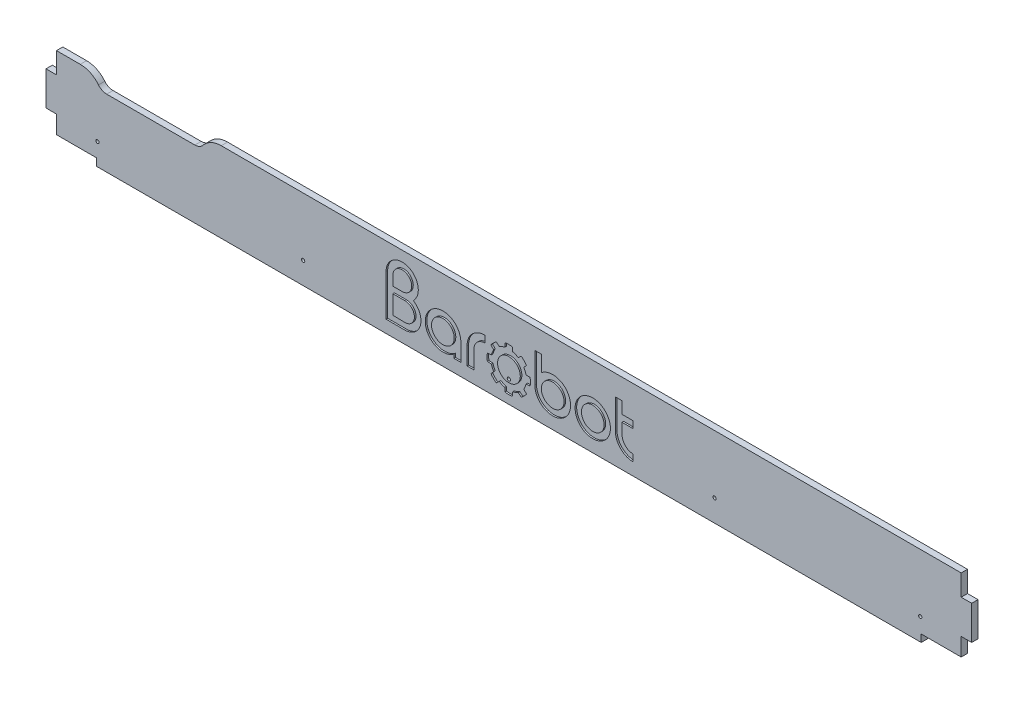
SolidWorks part; units mm, degrees
ref_plane "Płaszczyzna przednia" through (0, 0, 0) normal (0, 0, 1) x (1, 0, 0)
ref_plane "Płaszczyzna górna" through (0, 0, 0) normal (0, 1, 0) x (1, 0, 0)
ref_plane "Płaszczyzna prawa" through (0, 0, 0) normal (1, 0, 0) x (0, 0, -1)
sketch "Szkic2" plane through (0, 0, 0) normal (0, 0, 1) x (1, 0, 0)
  line L36 (-832, -462.604) -> (-48, -462.604)
  line L37 (-48, -462.604) -> (-48, -455.604)
  line L38 (-48, -455.604) -> (-10, -455.604)
  line L39 (-10, -455.604) -> (-10, -448.104)
  line L40 (-10, -438.604) -> (0, -438.604)
  line L41 (0, -438.604) -> (0, -406.324)
  line L42 (0, -406.324) -> (-10, -406.324)
  line L43 (-10, -406.324) -> (-10, -399.424)
  line L44 (-10, -386.324) -> (-713.4049, -386.324)
  line L45 (-738.497, -398.324) -> (-822.3149, -398.324)
  line L46 (-847.407, -386.324) -> (-870, -386.324)
  line L47 (-870, -386.324) -> (-870, -396.324)
  line L48 (-870, -406.324) -> (-880, -406.324)
  line L49 (-880, -406.324) -> (-880, -438.604)
  line L50 (-880, -438.604) -> (-870, -438.604)
  line L51 (-870, -438.604) -> (-870, -445.004)
  line L52 (-870, -455.604) -> (-832, -455.604)
  line L53 (-832, -455.604) -> (-832, -462.604)
  line L102 (-870, -396.324) -> (-870, -399.424)
  line L103 (-870, -445.004) -> (-870, -448.104)
  line L105 (-10, -396.324) -> (-10, -399.424)
  line L106 (-10, -445.004) -> (-10, -448.104)
  line L173 (-870, -448.104) -> (-870, -455.604)
  line L197 (-10, -445.004) -> (-10, -438.604)
  line L221 (-10, -396.324) -> (-10, -386.324)
  line L245 (-870, -399.424) -> (-870, -406.324)
  arc A8 (-713.4049, -386.324) -> (-730.7126, -394.6012) centre (-713.4049, -408.5578) ccw
  arc A9 (-738.497, -398.324) -> (-730.7126, -394.6012) centre (-738.497, -388.324) ccw
  arc A10 (-830.0993, -394.6012) -> (-822.3149, -398.324) centre (-822.3149, -388.324) ccw
  arc A11 (-830.0993, -394.6012) -> (-847.407, -386.324) centre (-847.407, -408.5578) ccw
extrude "Dodanie-wyciągnięcie1" add sketch "Szkic2" along normal blind 6
sketch "Szkic3" plane through (0, 0, 6) normal (0, 0, 1) x (1, 0, 0)
  circle A0 centre (-635.558, -441.7627) radius 1.55 construction
  circle A1 centre (-831.114, -441.7627) radius 1.55 construction
  circle A2 centre (-440.002, -441.7627) radius 1.55 construction
  circle A3 centre (-244.446, -441.7627) radius 1.55 construction
  circle A4 centre (-48.89, -441.7627) radius 1.55 construction
  circle A5 centre (-635.558, -441.7627) radius 1.55
  circle A6 centre (-831.114, -441.7627) radius 1.55
  circle A7 centre (-440.002, -441.7627) radius 1.55
  circle A8 centre (-244.446, -441.7627) radius 1.55
  circle A9 centre (-48.89, -441.7627) radius 1.55
extrude "Wytnij-wyciągnięcie1" cut sketch "Szkic3" against normal blind 6
sketch "Szkic18" plane through (0, 0, 6) normal (0, 0, 1) x (1, 0, 0)
  line L0 (-408.8752, -420.6037) -> (-408.8752, -420.833)
  line L2 (-550.3017, -411.4261) -> (-550.3017, -420.3981)
  line L3 (-550.3017, -444.3866) -> (-538.7617, -444.5821)
  line L4 (-541.3297, -420.3981) -> (-550.3017, -420.3981)
  line L5 (-538.7617, -426.6381) -> (-550.3017, -426.6381)
  line L6 (-550.3017, -426.6381) -> (-550.3017, -444.3866)
  circle A0 centre (-439.9185, -433.9811) radius 10.8
  circle A1 centre (-398.3185, -434.1758) radius 10.8
  circle A2 centre (-360.2385, -434.1673) radius 10.8
  circle A3 centre (-502.7185, -433.9811) radius 10.8
  arc A4 (-539.0655, -444.5769) -> (-538.7617, -426.6381) centre (-538.7617, -435.6101) ccw
  arc A5 (-541.3297, -420.3981) -> (-550.3017, -411.4261) centre (-541.3297, -411.4261) ccw
  circle A6 centre (-360.2385, -434.1673) radius 16.7971
  arc A7 (-321.883, -450.8241) -> (-338.774, -434.1673) centre (-321.8529, -433.9009) cw
  arc A8 (-415.3324, -434.1758) -> (-408.8752, -420.833) centre (-398.3185, -434.1758) ccw
  spline S0 degree 3 poles (-548.0079, -397.6111) (-547.8784, -397.5486) (-547.6175, -397.4274) (-547.2212, -397.257) (-546.8201, -397.0982) (-546.4147, -396.951) (-546.0053, -396.8154) (-545.5921, -396.6915) (-545.1757, -396.5793) (-544.7562, -396.4789) (-544.3341, -396.3904) (-543.9096, -396.3137) (-543.4832, -396.249) (-543.0551, -396.1962) (-542.6257, -396.1555) (-542.1953, -396.1269) (-541.7643, -396.1104) (-541.333, -396.1062) (-540.9017, -396.1141) (-540.4708, -396.1344) (-540.0406, -396.167) (-539.7546, -396.197) (-539.6118, -396.2141) knots 0 0 0 0 0.021232 0.042459 0.063684 0.084907 0.10613 0.127352 0.148575 0.169797 0.191021 0.212245 0.233469 0.254693 0.275917 0.297141 0.318365 0.33959 0.360814 0.38204 0.403268 0.424499 0.424499 0.424499 0.424499
  spline S1 degree 3 poles (-539.6118, -396.2141) (-539.4388, -396.2328) (-539.0937, -396.2767) (-538.5787, -396.3611) (-538.0672, -396.464) (-537.5598, -396.5849) (-537.0568, -396.7235) (-536.559, -396.8796) (-536.0668, -397.0529) (-535.5808, -397.243) (-535.1016, -397.4497) (-534.6296, -397.6726) (-534.1654, -397.9115) (-533.7096, -398.1661) (-533.2626, -398.436) (-532.8251, -398.721) (-532.3976, -399.0207) (-531.9806, -399.3349) (-531.5747, -399.6633) (-531.1804, -400.0055) (-530.7983, -400.3613) (-530.552, -400.6073) (-530.4311, -400.7325) knots 0 0 0 0 0.025683 0.051357 0.077025 0.102692 0.128359 0.154029 0.179702 0.205379 0.23106 0.256745 0.282432 0.308121 0.333811 0.359502 0.385192 0.410881 0.436569 0.462257 0.487946 0.513638 0.513638 0.513638 0.513638
  spline S2 degree 3 poles (-530.4311, -400.7325) (-530.302, -400.8635) (-530.0489, -401.1305) (-529.6846, -401.5448) (-529.3361, -401.9724) (-529.0037, -402.4124) (-528.6877, -402.8643) (-528.3885, -403.3273) (-528.1062, -403.8009) (-527.8411, -404.2844) (-527.5937, -404.7772) (-527.3642, -405.2784) (-527.1528, -405.7876) (-526.9599, -406.3041) (-526.7858, -406.8272) (-526.6308, -407.3562) (-526.4952, -407.8905) (-526.3792, -408.4295) (-526.2832, -408.9725) (-526.2075, -409.5187) (-526.1523, -410.0677) (-526.1295, -410.4349) (-526.1216, -410.6187) knots 0 0 0 0 0.027156 0.0543 0.081437 0.108569 0.135698 0.162826 0.189954 0.217081 0.244209 0.271336 0.298463 0.325588 0.352712 0.379836 0.406959 0.434083 0.46121 0.488344 0.515488 0.542648 0.542648 0.542648 0.542648
  spline S3 degree 3 poles (-526.1216, -410.6187) (-526.1122, -410.7808) (-526.099, -411.1051) (-526.0954, -411.5919) (-526.1078, -412.0782) (-526.136, -412.5637) (-526.18, -413.0479) (-526.2395, -413.5303) (-526.3145, -414.0104) (-526.4048, -414.4879) (-526.5102, -414.9623) (-526.6306, -415.433) (-526.7659, -415.8998) (-526.9159, -416.362) (-527.0804, -416.8192) (-527.2594, -417.2711) (-527.4527, -417.7171) (-527.6601, -418.1568) (-527.8815, -418.5897) (-528.1168, -419.0154) (-528.3658, -419.4334) (-528.5408, -419.7066) (-528.6305, -419.8417) knots 0 0 0 0 0.023966 0.047916 0.071852 0.09578 0.1197 0.143615 0.167527 0.191438 0.215347 0.239256 0.263166 0.287077 0.310989 0.334903 0.35882 0.38274 0.406665 0.430596 0.454535 0.478484 0.478484 0.478484 0.478484
  spline S4 degree 3 poles (-528.6305, -419.8417) (-528.6617, -419.8901) (-528.7249, -419.9862) (-528.8221, -420.1285) (-528.9217, -420.269) (-529.0232, -420.4079) (-529.1267, -420.5453) (-529.232, -420.6813) (-529.3388, -420.8161) (-529.4469, -420.9497) (-529.5564, -421.0824) (-529.6668, -421.2142) (-529.7782, -421.3452) (-529.8903, -421.4757) (-530.0029, -421.6058) (-530.1159, -421.7355) (-530.2291, -421.865) (-530.3424, -421.9944) (-530.4555, -422.124) (-530.5683, -422.2537) (-530.6807, -422.3837) (-530.7552, -422.4708) (-530.7923, -422.5144) knots 0 0 0 0 0.008494 0.016976 0.025449 0.033917 0.042381 0.050843 0.059304 0.067766 0.076228 0.084691 0.093156 0.101621 0.110087 0.118553 0.127019 0.135484 0.143948 0.152409 0.160867 0.169322 0.169322 0.169322 0.169322
  spline S5 degree 3 poles (-530.7923, -422.5144) (-530.6421, -422.6076) (-530.3449, -422.7995) (-529.9095, -423.1027) (-529.4849, -423.4209) (-529.0717, -423.7537) (-528.6702, -424.1005) (-528.2807, -424.4608) (-527.9039, -424.8343) (-527.5399, -425.2204) (-527.1894, -425.6186) (-526.8526, -426.0286) (-526.53, -426.4499) (-526.2221, -426.8818) (-525.9292, -427.3242) (-525.6517, -427.7763) (-525.3901, -428.2378) (-525.1448, -428.7083) (-524.9162, -429.1871) (-524.7047, -429.674) (-524.5108, -430.1683) (-524.3935, -430.5025) (-524.3379, -430.6706) knots 0 0 0 0 0.02611 0.052215 0.07832 0.104424 0.130528 0.156634 0.182739 0.208846 0.234952 0.261058 0.287162 0.313266 0.339368 0.365469 0.391571 0.417674 0.443782 0.469897 0.496023 0.522166 0.522166 0.522166 0.522166
  spline S6 degree 3 poles (-524.3379, -430.6706) (-524.2887, -430.8173) (-524.1948, -431.1122) (-524.0678, -431.5587) (-523.9545, -432.0088) (-523.8552, -432.462) (-523.7697, -432.9179) (-523.698, -433.3762) (-523.6402, -433.8363) (-523.5963, -434.298) (-523.5664, -434.7608) (-523.5503, -435.2242) (-523.5482, -435.6879) (-523.56, -436.1514) (-523.5857, -436.6143) (-523.6254, -437.0763) (-523.6791, -437.5368) (-523.7468, -437.9956) (-523.8285, -438.4521) (-523.9243, -438.9059) (-524.034, -439.3567) (-524.1165, -439.6549) (-524.1601, -439.8033) knots 0 0 0 0 0.022848 0.045688 0.068522 0.091351 0.114176 0.136999 0.15982 0.182639 0.205457 0.228273 0.251089 0.273904 0.296718 0.319532 0.342347 0.365163 0.387982 0.410804 0.433633 0.456469 0.456469 0.456469 0.456469
  spline S7 degree 3 poles (-524.1601, -439.8033) (-524.2091, -439.9748) (-524.3133, -440.3159) (-524.4884, -440.8213) (-524.6818, -441.3197) (-524.893, -441.8107) (-525.1216, -442.2937) (-525.3672, -442.7683) (-525.6293, -443.234) (-525.9075, -443.6903) (-526.2014, -444.1366) (-526.5107, -444.5726) (-526.8347, -444.9977) (-527.1733, -445.4114) (-527.5258, -445.8132) (-527.8919, -446.2027) (-528.2712, -446.5794) (-528.6632, -446.9427) (-529.0676, -447.2922) (-529.4838, -447.6274) (-529.9115, -447.9478) (-530.204, -448.1512) (-530.3521, -448.2502) knots 0 0 0 0 0.026332 0.052646 0.078949 0.105245 0.131537 0.157828 0.18412 0.210414 0.23671 0.263009 0.28931 0.315612 0.341914 0.368216 0.394517 0.420816 0.447113 0.473408 0.499701 0.525996 0.525996 0.525996 0.525996
  spline S8 degree 3 poles (-530.3521, -448.2502) (-530.4776, -448.3343) (-530.7314, -448.4987) (-531.1192, -448.7336) (-531.5139, -448.9567) (-531.9151, -449.1679) (-532.3223, -449.3671) (-532.7354, -449.5541) (-533.1538, -449.7288) (-533.5771, -449.8911) (-534.0051, -450.0408) (-534.4373, -450.1778) (-534.8733, -450.302) (-535.3129, -450.4132) (-535.7555, -450.5114) (-536.2009, -450.5963) (-536.6486, -450.6678) (-537.0982, -450.7259) (-537.5495, -450.7704) (-538.002, -450.8011) (-538.4553, -450.818) (-538.7578, -450.8198) (-538.909, -450.8184) knots 0 0 0 0 0.022313 0.044623 0.066933 0.089241 0.11155 0.13386 0.156169 0.178479 0.200789 0.223098 0.245408 0.267717 0.290025 0.312334 0.334643 0.356952 0.379264 0.40158 0.4239 0.446229 0.446229 0.446229 0.446229
  spline S9 degree 3 poles (-538.909, -450.8184) (-539.2052, -450.8179) (-539.7976, -450.8169) (-540.6862, -450.8161) (-541.5748, -450.8156) (-542.4633, -450.8156) (-543.3519, -450.8158) (-544.2405, -450.8163) (-545.1291, -450.8169) (-546.0177, -450.8175) (-546.9062, -450.8182) (-547.7948, -450.8188) (-548.6834, -450.8193) (-549.572, -450.8195) (-550.4605, -450.8194) (-551.3491, -450.819) (-552.2377, -450.8181) (-553.1263, -450.8167) (-554.0148, -450.8147) (-554.9034, -450.8121) (-555.792, -450.8087) (-556.3844, -450.8059) (-556.6806, -450.8043) knots 0 0 0 0 0.043729 0.087458 0.131188 0.174917 0.218646 0.262375 0.306104 0.349833 0.393563 0.437292 0.481021 0.52475 0.568479 0.612209 0.655938 0.699667 0.743396 0.787126 0.830855 0.874585 0.874585 0.874585 0.874585
  spline S10 degree 3 poles (-556.6806, -450.8043) (-556.68, -450.1497) (-556.679, -448.8405) (-556.6778, -446.8766) (-556.6768, -444.9128) (-556.6762, -442.949) (-556.6757, -440.9851) (-556.6754, -439.0213) (-556.6753, -437.0574) (-556.6753, -435.0936) (-556.6754, -433.1297) (-556.6756, -431.1659) (-556.6759, -429.2021) (-556.6761, -427.2382) (-556.6763, -425.2744) (-556.6765, -423.3105) (-556.6766, -421.3467) (-556.6766, -419.3828) (-556.6765, -417.419) (-556.6762, -415.4551) (-556.6757, -413.4913) (-556.6752, -412.1821) (-556.6749, -411.5275) knots 0 0 0 0 0.096646 0.193292 0.289938 0.386583 0.483229 0.579875 0.676521 0.773167 0.869812 0.966458 1.063104 1.15975 1.256396 1.353042 1.449687 1.546333 1.642979 1.739625 1.836271 1.932917 1.932917 1.932917 1.932917
  spline S11 degree 3 poles (-556.6749, -411.5275) (-556.6759, -411.4061) (-556.675, -411.1633) (-556.6651, -410.7993) (-556.6466, -410.4355) (-556.6196, -410.0723) (-556.5841, -409.7098) (-556.54, -409.3482) (-556.4874, -408.9878) (-556.4263, -408.6287) (-556.3568, -408.2711) (-556.2788, -407.9154) (-556.1923, -407.5616) (-556.0974, -407.2101) (-555.9941, -406.8609) (-555.8824, -406.5144) (-555.7623, -406.1707) (-555.6339, -405.8301) (-555.497, -405.4927) (-555.3519, -405.1588) (-555.1984, -404.8286) (-555.0905, -404.611) (-555.0352, -404.503) knots 0 0 0 0 0.017918 0.035839 0.053761 0.071685 0.089609 0.107534 0.125459 0.143383 0.161306 0.179227 0.197147 0.215066 0.232982 0.250898 0.268813 0.286727 0.304642 0.322558 0.340477 0.3584 0.3584 0.3584 0.3584
  spline S12 degree 3 poles (-555.0352, -404.503) (-554.9605, -404.3534) (-554.8058, -404.057) (-554.5588, -403.6206) (-554.2973, -403.1929) (-554.0217, -402.7743) (-553.7323, -402.3652) (-553.4295, -401.9659) (-553.1138, -401.5768) (-552.7855, -401.1982) (-552.4451, -400.8305) (-552.0928, -400.4741) (-551.7292, -400.1292) (-551.3546, -399.7964) (-550.9694, -399.4759) (-550.574, -399.1681) (-550.1687, -398.8734) (-549.7541, -398.5921) (-549.3304, -398.3246) (-548.8981, -398.0713) (-548.4575, -397.8325) (-548.1586, -397.6832) (-548.0079, -397.6111) knots 0 0 0 0 0.024682 0.049353 0.074017 0.098677 0.123334 0.14799 0.172645 0.197301 0.221958 0.246614 0.271271 0.295928 0.320584 0.34524 0.369894 0.394549 0.419202 0.443857 0.468514 0.493176 0.493176 0.493176 0.493176
  spline S13 degree 3 poles (-415.3324, -405.7645) (-415.2249, -405.7636) (-415.0099, -405.7621) (-414.6873, -405.7601) (-414.3649, -405.7584) (-414.0424, -405.7571) (-413.72, -405.7561) (-413.3976, -405.7553) (-413.0753, -405.7548) (-412.7529, -405.7545) (-412.4306, -405.7544) (-412.1084, -405.7546) (-411.7861, -405.7549) (-411.4639, -405.7553) (-411.1417, -405.7559) (-410.8195, -405.7566) (-410.4973, -405.7573) (-410.1751, -405.7582) (-409.8529, -405.759) (-409.5308, -405.7599) (-409.2086, -405.7608) (-408.9938, -405.7614) (-408.8864, -405.7617) knots 0 0 0 0 0.015874 0.031747 0.047617 0.063485 0.079352 0.095217 0.111081 0.126943 0.142804 0.158664 0.174523 0.190381 0.206238 0.222095 0.237951 0.253806 0.269661 0.285515 0.30137 0.317224 0.317224 0.317224 0.317224
  spline S14 degree 3 poles (-408.8864, -405.7617) (-408.8856, -406.009) (-408.8841, -406.5038) (-408.8825, -407.2459) (-408.8813, -407.988) (-408.8806, -408.7301) (-408.8803, -409.4722) (-408.8802, -410.2143) (-408.8804, -410.9564) (-408.8808, -411.6985) (-408.8813, -412.4406) (-408.8819, -413.1827) (-408.8824, -413.9248) (-408.8828, -414.6669) (-408.8831, -415.409) (-408.8832, -416.1511) (-408.8829, -416.8932) (-408.8824, -417.6353) (-408.8814, -418.3774) (-408.8799, -419.1195) (-408.8779, -419.8616) (-408.8761, -420.3564) (-408.8752, -420.6037) knots 0 0 0 0 0.036521 0.073042 0.109563 0.146084 0.182604 0.219125 0.255646 0.292167 0.328688 0.365209 0.401729 0.43825 0.474771 0.511292 0.547813 0.584334 0.620855 0.657375 0.693896 0.730417 0.730417 0.730417 0.730417
  spline S22 degree 3 poles (-415.3324, -434.1758) (-415.3321, -433.7022) (-415.3316, -432.7551) (-415.331, -431.3345) (-415.3305, -429.9139) (-415.3302, -428.4933) (-415.33, -427.0727) (-415.3299, -425.6522) (-415.3299, -424.2316) (-415.3299, -422.8111) (-415.3301, -421.3906) (-415.3303, -419.9701) (-415.3305, -418.5496) (-415.3308, -417.1291) (-415.331, -415.7086) (-415.3313, -414.2881) (-415.3316, -412.8676) (-415.3319, -411.447) (-415.3321, -410.0264) (-415.3323, -408.6058) (-415.3324, -407.1852) (-415.3324, -406.238) (-415.3324, -405.7645) knots 0 0 0 0 0.069916 0.139829 0.209742 0.279652 0.349562 0.41947 0.489378 0.559284 0.629191 0.699097 0.769003 0.83891 0.908817 0.978724 1.048633 1.118542 1.188453 1.258365 1.328279 1.398195 1.398195 1.398195 1.398195
  spline S23 degree 3 poles (-338.7683, -405.7645) (-338.6611, -405.7639) (-338.4465, -405.7628) (-338.1247, -405.7613) (-337.8028, -405.76) (-337.4808, -405.7588) (-337.1587, -405.7577) (-336.8366, -405.7568) (-336.5145, -405.7561) (-336.1923, -405.7555) (-335.8701, -405.7551) (-335.5478, -405.7549) (-335.2255, -405.7549) (-334.9033, -405.7551) (-334.581, -405.7555) (-334.2587, -405.7561) (-333.9364, -405.7569) (-333.6141, -405.7579) (-333.2918, -405.7592) (-332.9696, -405.7607) (-332.6474, -405.7624) (-332.4326, -405.7638) (-332.3252, -405.7645) knots 0 0 0 0 0.015836 0.031675 0.047518 0.063364 0.079213 0.095064 0.110918 0.126774 0.142631 0.15849 0.17435 0.19021 0.206071 0.221933 0.237793 0.253654 0.269513 0.285372 0.301229 0.317085 0.317085 0.317085 0.317085
  spline S24 degree 3 poles (-332.3252, -405.7645) (-332.3251, -405.9519) (-332.3249, -406.3266) (-332.3249, -406.8888) (-332.325, -407.4509) (-332.3254, -408.0129) (-332.3259, -408.575) (-332.3265, -409.137) (-332.3271, -409.699) (-332.3277, -410.261) (-332.3283, -410.823) (-332.3288, -411.3849) (-332.3291, -411.9469) (-332.3293, -412.5089) (-332.3293, -413.0709) (-332.329, -413.6329) (-332.3284, -414.1949) (-332.3275, -414.757) (-332.3262, -415.319) (-332.3245, -415.8811) (-332.3223, -416.4432) (-332.3205, -416.818) (-332.3196, -417.0054) knots 0 0 0 0 0.027666 0.05533 0.082992 0.110652 0.138312 0.16597 0.193628 0.221285 0.248941 0.276598 0.304254 0.33191 0.359567 0.387225 0.414883 0.442543 0.470203 0.497866 0.52553 0.553196 0.553196 0.553196 0.553196
  spline S25 degree 3 poles (-332.3196, -417.0054) (-332.1456, -417.0065) (-331.7976, -417.0085) (-331.2757, -417.0109) (-330.7538, -417.0127) (-330.232, -417.014) (-329.7102, -417.0148) (-329.1884, -417.0152) (-328.6667, -417.0153) (-328.145, -417.0151) (-327.6233, -417.0147) (-327.1016, -417.0142) (-326.58, -417.0137) (-326.0584, -417.0131) (-325.5367, -417.0126) (-325.0152, -417.0123) (-324.4936, -417.0121) (-323.972, -417.0122) (-323.4504, -417.0126) (-322.9289, -417.0135) (-322.4073, -417.0148) (-322.0596, -417.016) (-321.8858, -417.0167) knots 0 0 0 0 0.025687 0.051372 0.077055 0.102736 0.128415 0.154092 0.179769 0.205443 0.231117 0.256789 0.282461 0.308131 0.333801 0.35947 0.385138 0.410806 0.436473 0.46214 0.487807 0.513474 0.513474 0.513474 0.513474
  spline S26 degree 3 poles (-321.8858, -417.0167) (-321.8848, -417.1248) (-321.8829, -417.341) (-321.8805, -417.6652) (-321.8783, -417.9895) (-321.8765, -418.3138) (-321.875, -418.6381) (-321.8738, -418.9623) (-321.8728, -419.2866) (-321.8722, -419.6109) (-321.8718, -419.9351) (-321.8716, -420.2594) (-321.8718, -420.5837) (-321.8721, -420.908) (-321.8727, -421.2322) (-321.8736, -421.5565) (-321.8746, -421.8808) (-321.8759, -422.2051) (-321.8774, -422.5293) (-321.8791, -422.8536) (-321.8809, -423.1779) (-321.8823, -423.3941) (-321.883, -423.5021) knots 0 0 0 0 0.015959 0.031918 0.047876 0.063835 0.079793 0.095752 0.11171 0.127669 0.143627 0.159585 0.175544 0.191502 0.20746 0.223419 0.239377 0.255335 0.271294 0.287252 0.303211 0.31917 0.31917 0.31917 0.31917
  spline S27 degree 3 poles (-321.883, -423.5021) (-322.057, -423.5029) (-322.4049, -423.5041) (-322.9268, -423.5054) (-323.4487, -423.5064) (-323.9706, -423.5069) (-324.4924, -423.5071) (-325.0142, -423.5071) (-325.536, -423.5069) (-326.0577, -423.5065) (-326.5795, -423.5061) (-327.1013, -423.5057) (-327.623, -423.5053) (-328.1448, -423.505) (-328.6666, -423.5048) (-329.1883, -423.5049) (-329.7102, -423.5053) (-330.232, -423.506) (-330.7538, -423.5071) (-331.2757, -423.5086) (-331.7976, -423.5107) (-332.1456, -423.5124) (-332.3196, -423.5134) knots 0 0 0 0 0.025687 0.051371 0.077054 0.102736 0.128416 0.154095 0.179773 0.205451 0.231128 0.256805 0.282483 0.30816 0.333838 0.359516 0.385195 0.410876 0.436557 0.46224 0.487925 0.513612 0.513612 0.513612 0.513612
  spline S28 degree 3 poles (-332.3196, -423.5134) (-332.3204, -423.6642) (-332.3219, -423.9656) (-332.3238, -424.4179) (-332.3253, -424.8702) (-332.3264, -425.3225) (-332.3273, -425.775) (-332.3278, -426.2275) (-332.3281, -426.68) (-332.3283, -427.1326) (-332.3282, -427.5852) (-332.328, -428.0378) (-332.3278, -428.4905) (-332.3275, -428.9431) (-332.3272, -429.3958) (-332.3269, -429.8485) (-332.3267, -430.3012) (-332.3266, -430.7539) (-332.3266, -431.2065) (-332.3268, -431.6591) (-332.3273, -432.1117) (-332.3277, -432.4135) (-332.328, -432.5643) knots 0 0 0 0 0.022252 0.044508 0.066768 0.089031 0.111296 0.133564 0.155835 0.178107 0.200382 0.222657 0.244934 0.267211 0.289488 0.311766 0.334044 0.356321 0.378597 0.400872 0.423146 0.445418 0.445418 0.445418 0.445418
  spline S29 degree 3 poles (-332.328, -432.5643) (-332.3287, -432.6301) (-332.33, -432.7618) (-332.3315, -432.9594) (-332.3321, -433.1573) (-332.3318, -433.3552) (-332.3302, -433.5533) (-332.3271, -433.7514) (-332.3224, -433.9495) (-332.3156, -434.1475) (-332.3067, -434.3453) (-332.2953, -434.543) (-332.2813, -434.7405) (-332.2643, -434.9377) (-332.2443, -435.1346) (-332.2208, -435.3311) (-332.1937, -435.5271) (-332.1628, -435.7226) (-332.1278, -435.9177) (-332.0884, -436.1121) (-332.0445, -436.3058) (-332.012, -436.4344) (-331.995, -436.4985) knots 0 0 0 0 0.009716 0.019443 0.02918 0.038923 0.048671 0.058421 0.068172 0.077922 0.08767 0.097416 0.107158 0.116898 0.126635 0.136372 0.14611 0.155851 0.165599 0.175358 0.185133 0.194929 0.194929 0.194929 0.194929
  spline S30 degree 3 poles (-331.995, -436.4985) (-331.9607, -436.634) (-331.8864, -436.9037) (-331.7583, -437.3031) (-331.6139, -437.6968) (-331.4535, -438.0842) (-331.2776, -438.4649) (-331.0866, -438.8383) (-330.8809, -439.2038) (-330.6608, -439.5609) (-330.4269, -439.909) (-330.1793, -440.2477) (-329.9187, -440.5764) (-329.6452, -440.8945) (-329.3595, -441.2016) (-329.0617, -441.497) (-328.7524, -441.7802) (-328.4319, -442.0508) (-328.1007, -442.3081) (-327.759, -442.5516) (-327.4074, -442.7808) (-327.1667, -442.9236) (-327.0448, -442.9924) knots 0 0 0 0 0.020644 0.041279 0.06191 0.08254 0.10317 0.123803 0.144438 0.165075 0.185714 0.206354 0.226994 0.247632 0.26827 0.288905 0.309539 0.330173 0.350808 0.371448 0.392096 0.412758 0.412758 0.412758 0.412758
  spline S31 degree 3 poles (-327.0448, -442.9924) (-326.967, -443.0384) (-326.8102, -443.1277) (-326.571, -443.2541) (-326.3286, -443.373) (-326.083, -443.4846) (-325.8344, -443.5888) (-325.5831, -443.686) (-325.3293, -443.7763) (-325.0731, -443.8598) (-324.8148, -443.9366) (-324.5544, -444.007) (-324.2923, -444.0711) (-324.0287, -444.1289) (-323.7636, -444.1807) (-323.4974, -444.2267) (-323.2302, -444.2669) (-322.9622, -444.3016) (-322.6935, -444.3308) (-322.4245, -444.3547) (-322.1552, -444.3735) (-321.9756, -444.3828) (-321.8858, -444.3866) knots 0 0 0 0 0.013338 0.026646 0.039932 0.053202 0.066463 0.07972 0.092975 0.106233 0.119496 0.132765 0.146041 0.159325 0.172614 0.18591 0.199209 0.212509 0.225807 0.2391 0.252384 0.265654 0.265654 0.265654 0.265654
  spline S32 degree 3 poles (-321.8858, -444.3866) (-321.8848, -444.494) (-321.883, -444.7087) (-321.8805, -445.0308) (-321.8785, -445.3529) (-321.8768, -445.6749) (-321.8754, -445.9969) (-321.8743, -446.3188) (-321.8735, -446.6408) (-321.873, -446.9627) (-321.8727, -447.2845) (-321.8727, -447.6064) (-321.8729, -447.9282) (-321.8734, -448.25) (-321.874, -448.5718) (-321.8748, -448.8936) (-321.8758, -449.2154) (-321.877, -449.5371) (-321.8783, -449.8589) (-321.8798, -450.1806) (-321.8813, -450.5023) (-321.8824, -450.7168) (-321.883, -450.8241) knots 0 0 0 0 0.015854 0.031705 0.047555 0.063403 0.079249 0.095093 0.110936 0.126778 0.142618 0.158457 0.174295 0.190132 0.205968 0.221804 0.237639 0.253473 0.269308 0.285141 0.300975 0.316809 0.316809 0.316809 0.316809
  spline S35 degree 3 poles (-338.774, -434.1673) (-338.7737, -433.6939) (-338.7732, -432.7471) (-338.7727, -431.3269) (-338.7724, -429.9067) (-338.7723, -428.4865) (-338.7723, -427.0664) (-338.7724, -425.6462) (-338.7726, -424.2261) (-338.7728, -422.8061) (-338.773, -421.386) (-338.7733, -419.9659) (-338.7735, -418.5458) (-338.7736, -417.1258) (-338.7736, -415.7057) (-338.7735, -414.2856) (-338.7732, -412.8655) (-338.7727, -411.4453) (-338.7721, -410.0251) (-338.7711, -408.605) (-338.7699, -407.1847) (-338.7689, -406.2379) (-338.7683, -405.7645) knots 0 0 0 0 0.069895 0.139788 0.209679 0.279569 0.349457 0.419345 0.489232 0.559118 0.629003 0.698889 0.768774 0.83866 0.908546 0.978433 1.04832 1.118209 1.188099 1.25799 1.327883 1.397778 1.397778 1.397778 1.397778
  spline S36 degree 3 poles (-443.6675, -413.5905) (-443.5491, -413.5702) (-443.312, -413.5315) (-442.9555, -413.4796) (-442.5982, -413.4336) (-442.2402, -413.3937) (-441.8816, -413.3599) (-441.5226, -413.3322) (-441.1632, -413.3107) (-440.8035, -413.2953) (-440.4436, -413.2862) (-440.0836, -413.2832) (-439.7237, -413.2866) (-439.3639, -413.2962) (-439.0043, -413.3122) (-438.645, -413.3345) (-438.2862, -413.3632) (-437.9278, -413.3983) (-437.5701, -413.4399) (-437.2131, -413.4879) (-436.8569, -413.5425) (-436.6201, -413.5832) (-436.5019, -413.6046) knots 0 0 0 0 0.017733 0.035464 0.053192 0.070918 0.088641 0.106362 0.124081 0.141797 0.159513 0.177226 0.194939 0.212652 0.230365 0.248079 0.265794 0.283512 0.301234 0.31896 0.336692 0.354431 0.354431 0.354431 0.354431
  spline S37 degree 3 poles (-436.5019, -413.6046) (-436.5016, -413.6681) (-436.5003, -413.795) (-436.4963, -413.9854) (-436.4905, -414.1756) (-436.4831, -414.3657) (-436.4743, -414.5558) (-436.4643, -414.7458) (-436.4533, -414.9357) (-436.4416, -415.1256) (-436.4294, -415.3155) (-436.4169, -415.5054) (-436.4042, -415.6952) (-436.3917, -415.8851) (-436.3795, -416.075) (-436.3678, -416.265) (-436.3569, -416.455) (-436.3469, -416.645) (-436.3381, -416.8352) (-436.3307, -417.0254) (-436.3249, -417.2157) (-436.3222, -417.3427) (-436.3213, -417.4061) knots 0 0 0 0 0.009372 0.018741 0.028106 0.037471 0.046834 0.056197 0.06556 0.074923 0.084286 0.093651 0.103015 0.11238 0.121745 0.13111 0.140475 0.149841 0.159208 0.168576 0.177947 0.187321 0.187321 0.187321 0.187321
  spline S38 degree 3 poles (-436.3213, -417.4061) (-436.2298, -417.43) (-436.0474, -417.4789) (-435.7748, -417.5561) (-435.5034, -417.637) (-435.2333, -417.7216) (-434.9645, -417.8099) (-434.6969, -417.9018) (-434.4308, -417.9973) (-434.166, -418.0965) (-433.9026, -418.1992) (-433.6406, -418.3055) (-433.3802, -418.4153) (-433.1212, -418.5287) (-432.8638, -418.6455) (-432.608, -418.7658) (-432.3538, -418.8895) (-432.1013, -419.0167) (-431.8504, -419.1472) (-431.6013, -419.2811) (-431.3539, -419.4184) (-431.1902, -419.5121) (-431.1086, -419.5595) knots 0 0 0 0 0.013948 0.027889 0.041823 0.055753 0.069677 0.083598 0.097516 0.11143 0.125343 0.139254 0.153164 0.167074 0.180984 0.194895 0.208808 0.222722 0.236638 0.250558 0.26448 0.278406 0.278406 0.278406 0.278406
  spline S39 degree 3 poles (-431.1086, -419.5595) (-431.0629, -419.5176) (-430.9715, -419.4337) (-430.8346, -419.3076) (-430.6978, -419.1815) (-430.5611, -419.0553) (-430.4244, -418.929) (-430.2876, -418.8029) (-430.1507, -418.6769) (-430.0136, -418.5511) (-429.8764, -418.4256) (-429.7388, -418.3004) (-429.601, -418.1756) (-429.4628, -418.0513) (-429.3241, -417.9275) (-429.185, -417.8043) (-429.0454, -417.6818) (-428.9051, -417.56) (-428.7643, -417.439) (-428.6227, -417.3188) (-428.4804, -417.1996) (-428.385, -417.1208) (-428.3372, -417.0816) knots 0 0 0 0 0.009157 0.018315 0.027473 0.036631 0.045788 0.054946 0.064102 0.073257 0.082411 0.091563 0.100714 0.109863 0.119009 0.128154 0.137296 0.146437 0.155575 0.164712 0.173847 0.182981 0.182981 0.182981 0.182981
  spline S40 degree 3 poles (-428.3372, -417.0816) (-428.321, -417.0854) (-428.289, -417.0937) (-428.2416, -417.1084) (-428.195, -417.1251) (-428.1493, -417.1436) (-428.1043, -417.1638) (-428.06, -417.1855) (-428.0164, -417.2088) (-427.9734, -417.2333) (-427.931, -417.259) (-427.889, -417.2857) (-427.8476, -417.3134) (-427.8066, -417.3418) (-427.7659, -417.3709) (-427.7256, -417.4004) (-427.6855, -417.4304) (-427.6457, -417.4606) (-427.6061, -417.4909) (-427.5666, -417.5212) (-427.5272, -417.5513) (-427.5009, -417.5712) (-427.4877, -417.5811) knots 0 0 0 0 0.002452 0.004891 0.007321 0.009747 0.012173 0.0146 0.017031 0.019467 0.021908 0.024356 0.026808 0.029265 0.031725 0.034187 0.036649 0.039109 0.041565 0.044014 0.046456 0.048887 0.048887 0.048887 0.048887
  spline S41 degree 3 poles (-427.4877, -417.5811) (-427.4063, -417.6455) (-427.2443, -417.7753) (-427.0041, -417.9734) (-426.7667, -418.1748) (-426.5321, -418.3795) (-426.3003, -418.5874) (-426.0715, -418.7985) (-425.8456, -419.0128) (-425.6228, -419.2302) (-425.403, -419.4508) (-425.1864, -419.6744) (-424.9729, -419.901) (-424.7627, -420.1306) (-424.5557, -420.3632) (-424.3521, -420.5986) (-424.1518, -420.837) (-423.955, -421.0782) (-423.7616, -421.3223) (-423.5718, -421.5691) (-423.3856, -421.8186) (-423.2638, -421.9868) (-423.2036, -422.0713) knots 0 0 0 0 0.015322 0.030643 0.045965 0.061287 0.076609 0.091931 0.107253 0.122574 0.137896 0.153216 0.168537 0.183858 0.199178 0.214499 0.229819 0.24514 0.260461 0.275784 0.291107 0.306431 0.306431 0.306431 0.306431
  spline S42 degree 3 poles (-423.2036, -422.0713) (-423.2444, -422.1204) (-423.3263, -422.2183) (-423.4502, -422.3641) (-423.5751, -422.5092) (-423.7009, -422.6535) (-423.8273, -422.7971) (-423.9544, -422.9402) (-424.082, -423.0828) (-424.21, -423.225) (-424.3383, -423.3668) (-424.4668, -423.5085) (-424.5955, -423.65) (-424.7241, -423.7916) (-424.8527, -423.9331) (-424.981, -424.0748) (-425.109, -424.2167) (-425.2366, -424.359) (-425.3637, -424.5016) (-425.4902, -424.6447) (-425.616, -424.7885) (-425.6993, -424.8848) (-425.7408, -424.933) knots 0 0 0 0 0.009423 0.018844 0.028263 0.037682 0.047099 0.056516 0.065932 0.075348 0.084763 0.094176 0.103589 0.113 0.12241 0.131818 0.141224 0.150629 0.160031 0.169431 0.178829 0.188226 0.188226 0.188226 0.188226
  spline S43 degree 3 poles (-425.7408, -424.933) (-425.6936, -425.0143) (-425.6004, -425.1774) (-425.4637, -425.4238) (-425.3302, -425.6719) (-425.2, -425.9217) (-425.0731, -426.1732) (-424.9497, -426.4262) (-424.8296, -426.6809) (-424.7131, -426.9372) (-424.6002, -427.195) (-424.4909, -427.4544) (-424.3854, -427.7153) (-424.2836, -427.9777) (-424.1856, -428.2416) (-424.0915, -428.507) (-424.0014, -428.7738) (-423.9152, -429.042) (-423.8332, -429.3116) (-423.7552, -429.5826) (-423.6815, -429.8549) (-423.6352, -430.0373) (-423.6128, -430.1287) knots 0 0 0 0 0.01387 0.027738 0.041603 0.055465 0.069325 0.083182 0.097037 0.11089 0.124741 0.138592 0.152443 0.166294 0.180146 0.194001 0.207859 0.221721 0.235589 0.249465 0.263349 0.277244 0.277244 0.277244 0.277244
  spline S44 degree 3 poles (-423.6128, -430.1287) (-423.5493, -430.1304) (-423.4223, -430.1342) (-423.2319, -430.1411) (-423.0414, -430.149) (-422.8511, -430.1578) (-422.6607, -430.1674) (-422.4703, -430.1777) (-422.28, -430.1886) (-422.0896, -430.1998) (-421.8992, -430.2114) (-421.7088, -430.2233) (-421.5184, -430.2352) (-421.328, -430.247) (-421.1375, -430.2587) (-420.947, -430.2702) (-420.7565, -430.2812) (-420.5659, -430.2918) (-420.3752, -430.3017) (-420.1845, -430.3108) (-419.9937, -430.3191) (-419.8664, -430.324) (-419.8028, -430.3263) knots 0 0 0 0 0.009378 0.018756 0.028135 0.037515 0.046896 0.056277 0.065661 0.075045 0.084431 0.093818 0.103207 0.112597 0.121988 0.13138 0.140773 0.150168 0.159564 0.168961 0.17836 0.18776 0.18776 0.18776 0.18776
  spline S45 degree 3 poles (-419.8028, -430.3263) (-419.7812, -430.4442) (-419.7404, -430.6806) (-419.6863, -431.0361) (-419.6392, -431.3927) (-419.5988, -431.7501) (-419.5651, -432.1082) (-419.538, -432.4669) (-419.5173, -432.8261) (-419.5029, -433.1857) (-419.4946, -433.5456) (-419.4924, -433.9056) (-419.4961, -434.2656) (-419.5056, -434.6256) (-419.5207, -434.9854) (-419.5413, -435.3449) (-419.5674, -435.704) (-419.5986, -436.0625) (-419.6351, -436.4204) (-419.6765, -436.7775) (-419.7228, -437.1338) (-419.7568, -437.3708) (-419.7746, -437.4891) knots 0 0 0 0 0.017703 0.035402 0.0531 0.070798 0.088498 0.1062 0.123906 0.141616 0.15933 0.177047 0.194767 0.212488 0.23021 0.247931 0.265648 0.28336 0.301064 0.318757 0.336437 0.354101 0.354101 0.354101 0.354101
  spline S46 degree 3 poles (-419.7746, -437.4891) (-419.8382, -437.4954) (-419.9655, -437.5077) (-420.1566, -437.5247) (-420.3477, -437.5405) (-420.5388, -437.5551) (-420.7301, -437.5686) (-420.9213, -437.5811) (-421.1126, -437.5927) (-421.3039, -437.6034) (-421.4953, -437.6133) (-421.6866, -437.6225) (-421.878, -437.6311) (-422.0693, -437.6391) (-422.2606, -437.6467) (-422.4519, -437.6538) (-422.6432, -437.6606) (-422.8344, -437.6671) (-423.0256, -437.6735) (-423.2167, -437.6797) (-423.4077, -437.686) (-423.535, -437.6902) (-423.5987, -437.6923) knots 0 0 0 0 0.009441 0.01888 0.028317 0.037752 0.047186 0.056619 0.06605 0.07548 0.084909 0.094337 0.103763 0.113187 0.12261 0.13203 0.141449 0.150865 0.160278 0.169688 0.179094 0.188497 0.188497 0.188497 0.188497
  spline S47 degree 3 poles (-423.5987, -437.6923) (-423.6222, -437.7833) (-423.6706, -437.965) (-423.7466, -438.2365) (-423.8262, -438.507) (-423.9094, -438.7763) (-423.9963, -439.0444) (-424.0867, -439.3113) (-424.1808, -439.5768) (-424.2785, -439.8411) (-424.3799, -440.1038) (-424.485, -440.3652) (-424.5937, -440.625) (-424.7061, -440.8832) (-424.8223, -441.1398) (-424.9421, -441.3947) (-425.0657, -441.6479) (-425.1931, -441.8992) (-425.3242, -442.1487) (-425.459, -442.3963) (-425.5977, -442.642) (-425.6926, -442.8043) (-425.7408, -442.8852) knots 0 0 0 0 0.013879 0.027756 0.04163 0.055501 0.06937 0.083237 0.097102 0.110965 0.124826 0.138686 0.152546 0.166405 0.180266 0.194127 0.20799 0.221857 0.235727 0.249602 0.263482 0.27737 0.27737 0.27737 0.27737
  spline S48 degree 3 poles (-425.7408, -442.8852) (-425.6997, -442.934) (-425.6172, -443.0313) (-425.4925, -443.1765) (-425.367, -443.3209) (-425.2408, -443.4647) (-425.1139, -443.6079) (-424.9864, -443.7507) (-424.8586, -443.893) (-424.7304, -444.0351) (-424.6021, -444.177) (-424.4736, -444.3189) (-424.3451, -444.4607) (-424.2167, -444.6026) (-424.0886, -444.7447) (-423.9607, -444.8871) (-423.8333, -445.0298) (-423.7064, -445.173) (-423.5801, -445.3168) (-423.4546, -445.4612) (-423.3299, -445.6064) (-423.2475, -445.7037) (-423.2064, -445.7525) knots 0 0 0 0 0.009418 0.018835 0.028252 0.037668 0.047085 0.056501 0.065918 0.075336 0.084753 0.09417 0.103588 0.113005 0.122422 0.131839 0.141256 0.150672 0.160089 0.169505 0.178922 0.18834 0.18834 0.18834 0.18834
  spline S49 degree 3 poles (-423.2064, -445.7525) (-423.275, -445.8509) (-423.4139, -446.0462) (-423.6277, -446.3352) (-423.8468, -446.6202) (-424.0709, -446.9011) (-424.3, -447.1779) (-424.534, -447.4505) (-424.7727, -447.7191) (-425.016, -447.9834) (-425.2638, -448.2436) (-425.516, -448.4996) (-425.7725, -448.7514) (-426.0331, -448.999) (-426.2977, -449.2423) (-426.5661, -449.4813) (-426.8384, -449.7161) (-427.1143, -449.9465) (-427.3937, -450.1726) (-427.6766, -450.3944) (-427.9627, -450.6118) (-428.1556, -450.7538) (-428.2525, -450.8241) knots 0 0 0 0 0.017698 0.03539 0.053076 0.070759 0.088441 0.106121 0.123801 0.141483 0.159165 0.176849 0.194535 0.212222 0.229911 0.247601 0.265291 0.282981 0.300671 0.318358 0.336042 0.353722 0.353722 0.353722 0.353722
  spline S50 degree 3 poles (-428.2525, -450.8241) (-428.3019, -450.7835) (-428.4004, -450.7019) (-428.5473, -450.5785) (-428.6934, -450.4544) (-428.8388, -450.3294) (-428.9835, -450.2037) (-429.1277, -450.0774) (-429.2713, -449.9504) (-429.4144, -449.8229) (-429.557, -449.6949) (-429.6993, -449.5665) (-429.8413, -449.4377) (-429.983, -449.3087) (-430.1245, -449.1793) (-430.2659, -449.0499) (-430.4072, -448.9203) (-430.5484, -448.7906) (-430.6897, -448.661) (-430.831, -448.5314) (-430.9725, -448.402) (-431.067, -448.3158) (-431.1143, -448.2728) knots 0 0 0 0 0.009441 0.01888 0.028317 0.037751 0.047185 0.056618 0.066051 0.075483 0.084915 0.094348 0.10378 0.113213 0.122647 0.132081 0.141516 0.150951 0.160387 0.169823 0.179261 0.188699 0.188699 0.188699 0.188699
  spline S51 degree 3 poles (-431.1143, -448.2728) (-431.1957, -448.3202) (-431.3591, -448.414) (-431.6059, -448.5517) (-431.8543, -448.6863) (-432.1044, -448.8177) (-432.3561, -448.9458) (-432.6095, -449.0706) (-432.8645, -449.1918) (-433.121, -449.3096) (-433.3791, -449.4238) (-433.6388, -449.5342) (-433.9001, -449.6409) (-434.1628, -449.7438) (-434.4271, -449.8427) (-434.6929, -449.9377) (-434.9602, -450.0285) (-435.2289, -450.1151) (-435.4991, -450.1976) (-435.7708, -450.2756) (-436.0439, -450.3493) (-436.2268, -450.3954) (-436.3184, -450.4177) knots 0 0 0 0 0.01391 0.027817 0.041723 0.055625 0.069525 0.083422 0.097316 0.111208 0.125097 0.138985 0.152871 0.166758 0.180644 0.194532 0.208423 0.222319 0.23622 0.250128 0.264046 0.277976 0.277976 0.277976 0.277976
  spline S52 degree 3 poles (-436.3184, -450.4177) (-436.32, -450.4812) (-436.3236, -450.6081) (-436.3306, -450.7985) (-436.3388, -450.9889) (-436.3482, -451.1791) (-436.3585, -451.3694) (-436.3695, -451.5595) (-436.3811, -451.7497) (-436.3931, -451.9399) (-436.4054, -452.13) (-436.4176, -452.3202) (-436.4297, -452.5104) (-436.4415, -452.7006) (-436.4527, -452.8909) (-436.4633, -453.0812) (-436.473, -453.2716) (-436.4817, -453.4621) (-436.4891, -453.6526) (-436.4951, -453.8433) (-436.4995, -454.034) (-436.5013, -454.1612) (-436.5019, -454.2249) knots 0 0 0 0 0.009377 0.018752 0.028127 0.037502 0.046877 0.056253 0.065629 0.075006 0.084384 0.093762 0.103141 0.11252 0.1219 0.131281 0.140662 0.150045 0.159429 0.168816 0.178205 0.187599 0.187599 0.187599 0.187599
  spline S53 degree 3 poles (-436.5019, -454.2249) (-436.62, -454.2471) (-436.8565, -454.2894) (-437.2123, -454.3457) (-437.569, -454.3952) (-437.9265, -454.4377) (-438.2846, -454.4735) (-438.6432, -454.5026) (-439.0024, -454.5251) (-439.3619, -454.5409) (-439.7216, -454.5503) (-440.0815, -454.5533) (-440.4415, -454.5499) (-440.8015, -454.5402) (-441.1613, -454.5244) (-441.5208, -454.5024) (-441.8801, -454.4743) (-442.2388, -454.4402) (-442.5971, -454.4003) (-442.9547, -454.3544) (-443.3116, -454.3028) (-443.549, -454.2647) (-443.6675, -454.2446) knots 0 0 0 0 0.017739 0.035467 0.053187 0.070901 0.088611 0.106319 0.124026 0.141733 0.159442 0.177154 0.194869 0.212588 0.230311 0.248039 0.26577 0.283506 0.301246 0.318988 0.336734 0.354481 0.354481 0.354481 0.354481
  spline S54 degree 3 poles (-443.6675, -454.2446) (-443.6757, -454.1811) (-443.691, -454.0541) (-443.7111, -453.8633) (-443.7285, -453.6723) (-443.7437, -453.4812) (-443.7568, -453.2899) (-443.7682, -453.0985) (-443.7781, -452.907) (-443.7869, -452.7155) (-443.7947, -452.5239) (-443.802, -452.3322) (-443.8089, -452.1405) (-443.8158, -451.9489) (-443.823, -451.7572) (-443.8306, -451.5656) (-443.8392, -451.374) (-443.8488, -451.1825) (-443.8598, -450.9911) (-443.8725, -450.7998) (-443.8872, -450.6086) (-443.8985, -450.4813) (-443.9046, -450.4177) knots 0 0 0 0 0.009448 0.01889 0.028327 0.037763 0.047197 0.056632 0.066068 0.075504 0.084942 0.094381 0.103819 0.113258 0.122697 0.132135 0.141572 0.151008 0.160443 0.169877 0.179312 0.188749 0.188749 0.188749 0.188749
  spline S55 degree 3 poles (-443.9046, -450.4177) (-443.9953, -450.3944) (-444.1765, -450.3467) (-444.4472, -450.2715) (-444.7169, -450.1928) (-444.9854, -450.1104) (-445.2528, -450.0244) (-445.5189, -449.9347) (-445.7836, -449.8412) (-446.047, -449.744) (-446.309, -449.643) (-446.5694, -449.5381) (-446.8282, -449.4294) (-447.0854, -449.3168) (-447.3408, -449.2002) (-447.5945, -449.0796) (-447.8463, -448.9551) (-448.0962, -448.8264) (-448.3441, -448.6937) (-448.59, -448.5568) (-448.8338, -448.4158) (-448.9948, -448.3191) (-449.0749, -448.27) knots 0 0 0 0 0.013829 0.027656 0.041482 0.055305 0.069126 0.082945 0.096762 0.110578 0.124393 0.138208 0.152022 0.165838 0.179656 0.193477 0.207303 0.221134 0.234972 0.248819 0.262677 0.276548 0.276548 0.276548 0.276548
  spline S56 degree 3 poles (-449.0749, -448.27) (-449.1224, -448.3123) (-449.2175, -448.397) (-449.3601, -448.5242) (-449.5025, -448.6515) (-449.6449, -448.7789) (-449.7873, -448.9063) (-449.9296, -449.0339) (-450.0718, -449.1615) (-450.214, -449.2891) (-450.3562, -449.4168) (-450.4983, -449.5446) (-450.6405, -449.6723) (-450.7826, -449.8001) (-450.9247, -449.9278) (-451.0668, -450.0556) (-451.2089, -450.1833) (-451.351, -450.311) (-451.4931, -450.4387) (-451.6353, -450.5663) (-451.7775, -450.6938) (-451.8723, -450.7788) (-451.9197, -450.8213) knots 0 0 0 0 0.0094 0.018801 0.028203 0.037606 0.047009 0.056413 0.065817 0.075222 0.084626 0.094031 0.103436 0.11284 0.122244 0.131648 0.141051 0.150453 0.159855 0.169256 0.178655 0.188054 0.188054 0.188054 0.188054
  spline S57 degree 3 poles (-451.9197, -450.8213) (-452.0194, -450.7533) (-452.2175, -450.6153) (-452.5103, -450.4025) (-452.7987, -450.184) (-453.0828, -449.9601) (-453.3625, -449.7308) (-453.6378, -449.4963) (-453.9086, -449.2567) (-454.175, -449.0121) (-454.4369, -448.7628) (-454.6943, -448.5088) (-454.9472, -448.2504) (-455.1956, -447.9875) (-455.4395, -447.7205) (-455.6787, -447.4493) (-455.9134, -447.1742) (-456.1435, -446.8953) (-456.3689, -446.6128) (-456.5897, -446.3268) (-456.8059, -446.0373) (-456.9469, -445.8422) (-457.0166, -445.7441) knots 0 0 0 0 0.017821 0.035633 0.053438 0.071239 0.089036 0.106831 0.124626 0.14242 0.160214 0.178009 0.195805 0.213601 0.231397 0.249193 0.266987 0.284779 0.302567 0.32035 0.338127 0.355896 0.355896 0.355896 0.355896
  spline S58 degree 3 poles (-457.0166, -445.7441) (-456.9736, -445.6968) (-456.8876, -445.6021) (-456.759, -445.4599) (-456.6306, -445.3173) (-456.5024, -445.1745) (-456.3744, -445.0316) (-456.2465, -444.8885) (-456.1188, -444.7453) (-455.9911, -444.602) (-455.8634, -444.4586) (-455.7357, -444.3153) (-455.6079, -444.172) (-455.48, -444.0288) (-455.352, -443.8858) (-455.2238, -443.7428) (-455.0954, -443.6001) (-454.9667, -443.4576) (-454.8377, -443.3154) (-454.7084, -443.1735) (-454.5786, -443.0319) (-454.4919, -442.9378) (-454.4484, -442.8908) knots 0 0 0 0 0.009439 0.018879 0.02832 0.037762 0.047206 0.05665 0.066095 0.07554 0.084987 0.094434 0.103881 0.113329 0.122778 0.132226 0.141675 0.151124 0.160574 0.170023 0.179473 0.188923 0.188923 0.188923 0.188923
  spline S59 degree 3 poles (-454.4484, -442.8908) (-454.4974, -442.8105) (-454.594, -442.6493) (-454.7351, -442.4051) (-454.8723, -442.1589) (-455.0056, -441.9106) (-455.1351, -441.6604) (-455.2606, -441.4082) (-455.3821, -441.1541) (-455.4997, -440.8982) (-455.6133, -440.6405) (-455.7229, -440.3811) (-455.8286, -440.12) (-455.9302, -439.8573) (-456.0278, -439.593) (-456.1213, -439.3272) (-456.2108, -439.06) (-456.2962, -438.7913) (-456.3775, -438.5213) (-456.4548, -438.25) (-456.5278, -437.9775) (-456.5738, -437.795) (-456.5961, -437.7036) knots 0 0 0 0 0.013881 0.027758 0.041629 0.055497 0.069361 0.083223 0.097083 0.110943 0.124801 0.13866 0.15252 0.166381 0.180245 0.19411 0.207979 0.221851 0.235728 0.249609 0.263496 0.277388 0.277388 0.277388 0.277388
  spline S60 degree 3 poles (-456.5961, -437.7036) (-456.6599, -437.7003) (-456.7875, -437.6941) (-456.9791, -437.6853) (-457.1707, -437.677) (-457.3624, -437.6691) (-457.5541, -437.6613) (-457.746, -437.6538) (-457.9378, -437.6462) (-458.1297, -437.6384) (-458.3216, -437.6305) (-458.5135, -437.6222) (-458.7053, -437.6133) (-458.8971, -437.6039) (-459.0889, -437.5938) (-459.2806, -437.5828) (-459.4723, -437.5708) (-459.6638, -437.5577) (-459.8552, -437.5435) (-460.0465, -437.5279) (-460.2377, -437.5108) (-460.365, -437.4984) (-460.4287, -437.4919) knots 0 0 0 0 0.009431 0.018866 0.028305 0.037747 0.047192 0.05664 0.066089 0.07554 0.084991 0.094443 0.103895 0.113347 0.122798 0.132248 0.141697 0.151145 0.160592 0.170038 0.179483 0.188927 0.188927 0.188927 0.188927
  spline S61 degree 3 poles (-460.4287, -437.4919) (-460.4484, -437.3735) (-460.486, -437.1364) (-460.5367, -436.78) (-460.5816, -436.4228) (-460.6206, -436.0649) (-460.6538, -435.7065) (-460.681, -435.3477) (-460.7024, -434.9885) (-460.7177, -434.6291) (-460.727, -434.2695) (-460.7303, -433.9098) (-460.7274, -433.5502) (-460.7185, -433.1907) (-460.7033, -432.8315) (-460.682, -432.4726) (-460.6544, -432.1142) (-460.6205, -431.7562) (-460.5803, -431.3989) (-460.5337, -431.0423) (-460.4807, -430.6865) (-460.4411, -430.45) (-460.4202, -430.3319) knots 0 0 0 0 0.01772 0.035439 0.053155 0.07087 0.088582 0.106291 0.123998 0.141702 0.159403 0.177102 0.194799 0.212494 0.230187 0.247879 0.265571 0.283264 0.300958 0.318654 0.336354 0.354059 0.354059 0.354059 0.354059
  spline S62 degree 3 poles (-460.4202, -430.3319) (-460.3569, -430.3295) (-460.2302, -430.3243) (-460.0401, -430.3154) (-459.8501, -430.3056) (-459.6602, -430.295) (-459.4702, -430.2838) (-459.2803, -430.2721) (-459.0904, -430.2601) (-458.9004, -430.2479) (-458.7105, -430.2357) (-458.5205, -430.2236) (-458.3305, -430.2118) (-458.1405, -430.2004) (-457.9505, -430.1895) (-457.7604, -430.1794) (-457.5703, -430.1702) (-457.3801, -430.162) (-457.1898, -430.155) (-456.9995, -430.1493) (-456.8091, -430.1451) (-456.6822, -430.1434) (-456.6187, -430.1428) knots 0 0 0 0 0.009361 0.018723 0.028085 0.037448 0.046812 0.056177 0.065543 0.07491 0.084277 0.093644 0.103012 0.112379 0.121747 0.131115 0.140482 0.14985 0.159219 0.168589 0.17796 0.187334 0.187334 0.187334 0.187334
  spline S63 degree 3 poles (-456.6187, -430.1428) (-456.5941, -430.0517) (-456.544, -429.8696) (-456.4659, -429.5974) (-456.3845, -429.3261) (-456.3, -429.0558) (-456.2122, -428.7865) (-456.1211, -428.5185) (-456.0265, -428.2517) (-455.9283, -427.9863) (-455.8266, -427.7222) (-455.7212, -427.4597) (-455.6119, -427.1988) (-455.4989, -426.9395) (-455.3819, -426.682) (-455.2609, -426.4263) (-455.1358, -426.1725) (-455.0066, -425.9208) (-454.8731, -425.6711) (-454.7352, -425.4235) (-454.593, -425.1782) (-454.4952, -425.0164) (-454.4456, -424.9358) knots 0 0 0 0 0.013939 0.027878 0.041816 0.055754 0.069689 0.083622 0.097552 0.111479 0.125403 0.139325 0.153245 0.167163 0.181082 0.195002 0.208924 0.22285 0.236783 0.250725 0.264677 0.278644 0.278644 0.278644 0.278644
  spline S64 degree 3 poles (-454.4456, -424.9358) (-454.489, -424.8887) (-454.5759, -424.7944) (-454.7062, -424.6529) (-454.8363, -424.5112) (-454.9663, -424.3695) (-455.0962, -424.2276) (-455.2259, -424.0855) (-455.3554, -423.9433) (-455.4847, -423.8009) (-455.6139, -423.6584) (-455.7428, -423.5156) (-455.8715, -423.3726) (-455.9999, -423.2294) (-456.1281, -423.086) (-456.256, -422.9423) (-456.3836, -422.7983) (-456.5109, -422.6541) (-456.6378, -422.5096) (-456.7645, -422.3647) (-456.8908, -422.2196) (-456.9747, -422.1226) (-457.0166, -422.0741) knots 0 0 0 0 0.009465 0.018931 0.028397 0.037863 0.047329 0.056795 0.066262 0.075728 0.085194 0.094661 0.104128 0.113594 0.123061 0.132528 0.141995 0.151462 0.160929 0.170397 0.179864 0.189332 0.189332 0.189332 0.189332
  spline S65 degree 3 poles (-457.0166, -422.0741) (-456.9462, -421.9767) (-456.8039, -421.7829) (-456.5863, -421.4953) (-456.3645, -421.2109) (-456.1383, -420.9298) (-455.9079, -420.6522) (-455.6732, -420.3783) (-455.4341, -420.1082) (-455.1907, -419.8421) (-454.9429, -419.5801) (-454.6908, -419.3224) (-454.4343, -419.0692) (-454.1734, -418.8205) (-453.9081, -418.5766) (-453.6383, -418.3376) (-453.3641, -418.1037) (-453.0854, -417.875) (-452.8023, -417.6517) (-452.5147, -417.4339) (-452.2226, -417.2218) (-452.0249, -417.0844) (-451.9253, -417.0167) knots 0 0 0 0 0.017743 0.035492 0.053244 0.070997 0.08875 0.106503 0.124253 0.142001 0.159746 0.177487 0.195226 0.212962 0.230697 0.248431 0.266167 0.283906 0.30165 0.319402 0.337165 0.354942 0.354942 0.354942 0.354942
  spline S66 degree 3 poles (-451.9253, -417.0167) (-451.8769, -417.0582) (-451.7804, -417.1414) (-451.6363, -417.267) (-451.4927, -417.3932) (-451.3497, -417.52) (-451.2072, -417.6473) (-451.065, -417.775) (-450.9232, -417.903) (-450.7816, -418.0312) (-450.6401, -418.1596) (-450.4987, -418.2881) (-450.3573, -418.4166) (-450.2158, -418.545) (-450.0742, -418.6732) (-449.9324, -418.8012) (-449.7902, -418.9289) (-449.6477, -419.0562) (-449.5047, -419.183) (-449.3611, -419.3092) (-449.217, -419.4348) (-449.1205, -419.518) (-449.0721, -419.5595) knots 0 0 0 0 0.00941 0.018818 0.028225 0.03763 0.047034 0.056437 0.06584 0.075242 0.084645 0.094047 0.103449 0.112851 0.122253 0.131656 0.141059 0.150463 0.159868 0.169275 0.178683 0.188093 0.188093 0.188093 0.188093
  spline S67 degree 3 poles (-449.0721, -419.5595) (-448.9915, -419.5111) (-448.8297, -419.4156) (-448.5848, -419.2762) (-448.3378, -419.1407) (-448.0889, -419.009) (-447.838, -418.8811) (-447.5853, -418.7571) (-447.3308, -418.6368) (-447.0745, -418.5203) (-446.8166, -418.4075) (-446.557, -418.2984) (-446.2959, -418.193) (-446.0332, -418.0914) (-445.7691, -417.9934) (-445.5036, -417.899) (-445.2368, -417.8083) (-444.9688, -417.7212) (-444.6995, -417.6376) (-444.429, -417.5577) (-444.1575, -417.4813) (-443.9758, -417.4327) (-443.8848, -417.409) knots 0 0 0 0 0.013873 0.027741 0.041603 0.055461 0.069317 0.083171 0.097024 0.110878 0.124732 0.138587 0.152444 0.166304 0.180166 0.194031 0.207899 0.221771 0.235645 0.249524 0.263405 0.277289 0.277289 0.277289 0.277289
  spline S68 degree 3 poles (-443.8848, -417.409) (-443.8806, -417.3453) (-443.8727, -417.218) (-443.8622, -417.027) (-443.8528, -416.8359) (-443.8445, -416.6447) (-443.8369, -416.4536) (-443.8298, -416.2624) (-443.8231, -416.0712) (-443.8165, -415.88) (-443.8097, -415.6888) (-443.8027, -415.4976) (-443.7951, -415.3065) (-443.7868, -415.1155) (-443.7776, -414.9245) (-443.7671, -414.7335) (-443.7553, -414.5427) (-443.7419, -414.352) (-443.7267, -414.1614) (-443.7094, -413.9709) (-443.6899, -413.7806) (-443.6753, -413.6538) (-443.6675, -413.5905) knots 0 0 0 0 0.009416 0.018832 0.028247 0.037663 0.047079 0.056494 0.06591 0.075325 0.08474 0.094153 0.103566 0.112977 0.122388 0.131797 0.141205 0.150614 0.160024 0.169435 0.17885 0.188271 0.188271 0.188271 0.188271
  spline S69 degree 3 poles (-504.5513, -417.1352) (-504.3458, -417.1097) (-503.9337, -417.0666) (-503.3138, -417.0258) (-502.6928, -417.0087) (-502.0717, -417.015) (-501.4513, -417.0444) (-500.8324, -417.0969) (-500.2157, -417.1721) (-499.6022, -417.2699) (-498.9926, -417.39) (-498.3877, -417.5323) (-497.7884, -417.6965) (-497.1955, -417.8825) (-496.6098, -418.0899) (-496.0321, -418.3186) (-495.4633, -418.5684) (-494.9041, -418.8391) (-494.3553, -419.1305) (-493.8179, -419.4423) (-493.2926, -419.7743) (-492.9511, -420.009) (-492.7826, -420.1296) knots 0 0 0 0 0.030578 0.061145 0.091706 0.122265 0.152825 0.183387 0.213953 0.244521 0.275092 0.305665 0.336238 0.366811 0.397383 0.427953 0.458521 0.489087 0.519654 0.550222 0.580797 0.611383 0.611383 0.611383 0.611383
  spline S70 degree 3 poles (-492.7826, -420.1296) (-492.5684, -420.2802) (-492.1474, -420.592) (-491.5395, -421.0896) (-490.9563, -421.6155) (-490.3987, -422.1684) (-489.8675, -422.7467) (-489.3636, -423.349) (-488.8879, -423.9738) (-488.4413, -424.6198) (-488.0247, -425.2855) (-487.6388, -425.9694) (-487.2847, -426.6702) (-486.9631, -427.3863) (-486.675, -428.1164) (-486.4213, -428.8589) (-486.2028, -429.6125) (-486.0204, -430.3758) (-485.8749, -431.1472) (-485.7674, -431.9254) (-485.6986, -432.7088) (-485.6792, -433.2332) (-485.6763, -433.4956) knots 0 0 0 0 0.038665 0.077307 0.115938 0.154566 0.193194 0.231826 0.27046 0.309097 0.347732 0.386364 0.424991 0.463609 0.502219 0.540822 0.57942 0.618021 0.656634 0.695272 0.733953 0.772701 0.772701 0.772701 0.772701
  spline S71 degree 3 poles (-485.6763, -433.4956) (-485.6749, -433.7842) (-485.6723, -434.3613) (-485.6693, -435.227) (-485.667, -436.0926) (-485.6652, -436.9582) (-485.6641, -437.8237) (-485.6634, -438.6892) (-485.6631, -439.5547) (-485.6631, -440.4202) (-485.6634, -441.2856) (-485.6639, -442.151) (-485.6645, -443.0164) (-485.6651, -443.8818) (-485.6657, -444.7471) (-485.6661, -445.6125) (-485.6664, -446.4778) (-485.6664, -447.3431) (-485.6661, -448.2084) (-485.6653, -449.0737) (-485.6641, -449.939) (-485.6629, -450.5159) (-485.6622, -450.8043) knots 0 0 0 0 0.042604 0.085205 0.127804 0.170402 0.212998 0.255592 0.298185 0.340777 0.383367 0.425956 0.468544 0.511131 0.553717 0.596303 0.638888 0.681472 0.724056 0.76664 0.809223 0.851807 0.851807 0.851807 0.851807
  spline S72 degree 3 poles (-485.6622, -450.8043) (-485.7694, -450.8057) (-485.9839, -450.8083) (-486.3057, -450.8115) (-486.6276, -450.8141) (-486.9494, -450.8161) (-487.2713, -450.8176) (-487.5932, -450.8187) (-487.9151, -450.8193) (-488.237, -450.8196) (-488.559, -450.8195) (-488.8809, -450.8192) (-489.2029, -450.8186) (-489.5248, -450.818) (-489.8467, -450.8172) (-490.1686, -450.8163) (-490.4905, -450.8154) (-490.8124, -450.8146) (-491.1343, -450.8139) (-491.4561, -450.8133) (-491.7779, -450.8129) (-491.9924, -450.8128) (-492.0997, -450.8128) knots 0 0 0 0 0.015835 0.031672 0.047511 0.06335 0.079191 0.095033 0.110875 0.126719 0.142562 0.158406 0.174249 0.190093 0.205936 0.221779 0.23762 0.253461 0.2693 0.285138 0.300975 0.316809 0.316809 0.316809 0.316809
  spline S73 degree 3 poles (-492.0997, -450.8128) (-492.1004, -450.7528) (-492.1017, -450.6328) (-492.1033, -450.4529) (-492.1046, -450.2729) (-492.1057, -450.0928) (-492.1066, -449.9127) (-492.1072, -449.7326) (-492.1077, -449.5525) (-492.1079, -449.3723) (-492.1081, -449.1921) (-492.1081, -449.0119) (-492.1081, -448.8316) (-492.108, -448.6513) (-492.1079, -448.4711) (-492.1077, -448.2908) (-492.1076, -448.1105) (-492.1075, -447.9302) (-492.1075, -447.7498) (-492.1076, -447.5695) (-492.1078, -447.3892) (-492.108, -447.2689) (-492.1081, -447.2088) knots 0 0 0 0 0.008856 0.017713 0.026573 0.035434 0.044296 0.05316 0.062026 0.070893 0.079761 0.08863 0.0975 0.106371 0.115243 0.124116 0.13299 0.141864 0.150738 0.159613 0.168487 0.177362 0.177362 0.177362 0.177362
  spline S74 degree 3 poles (-492.1081, -447.2088) (-492.2185, -447.2945) (-492.4412, -447.4632) (-492.7812, -447.7085) (-493.1269, -447.9456) (-493.4781, -448.1746) (-493.8347, -448.3951) (-494.1964, -448.6071) (-494.563, -448.8103) (-494.9344, -449.0047) (-495.3103, -449.1899) (-495.6906, -449.3659) (-496.075, -449.5324) (-496.4635, -449.6893) (-496.8557, -449.8364) (-497.2515, -449.9736) (-497.6508, -450.1006) (-498.0532, -450.2173) (-498.4587, -450.3235) (-498.867, -450.4191) (-499.2779, -450.5039) (-499.5534, -450.553) (-499.6914, -450.5757) knots 0 0 0 0 0.020625 0.041254 0.061884 0.082515 0.103145 0.123774 0.144402 0.165027 0.185649 0.206268 0.226885 0.247499 0.268113 0.288726 0.309341 0.32996 0.350584 0.371216 0.391861 0.412521 0.412521 0.412521 0.412521
  spline S75 degree 3 poles (-499.6914, -450.5757) (-499.8694, -450.6068) (-500.2262, -450.663) (-500.7639, -450.7297) (-501.3035, -450.7789) (-501.8444, -450.8106) (-502.386, -450.8249) (-502.9278, -450.8218) (-503.4693, -450.8014) (-504.0098, -450.7638) (-504.5488, -450.709) (-505.0858, -450.6371) (-505.6203, -450.5482) (-506.1516, -450.4422) (-506.6792, -450.3193) (-507.2025, -450.1795) (-507.7211, -450.0229) (-508.2343, -449.8495) (-508.7417, -449.6594) (-509.2425, -449.4527) (-509.7364, -449.2294) (-510.0605, -449.0695) (-510.2212, -448.9868) knots 0 0 0 0 0.026664 0.053325 0.079984 0.106643 0.133301 0.159961 0.186621 0.213281 0.239941 0.2666 0.293259 0.319916 0.346571 0.373226 0.39988 0.426534 0.45319 0.47985 0.506517 0.533194 0.533194 0.533194 0.533194
  spline S76 degree 3 poles (-510.2212, -448.9868) (-510.4021, -448.8958) (-510.7606, -448.707) (-511.2873, -448.4039) (-511.8022, -448.0816) (-512.3049, -447.7406) (-512.7947, -447.3815) (-513.2713, -447.0049) (-513.734, -446.6114) (-514.1824, -446.2016) (-514.6159, -445.776) (-515.0339, -445.3352) (-515.4361, -444.8798) (-515.8217, -444.4104) (-516.1904, -443.9275) (-516.5416, -443.4318) (-516.8747, -442.9237) (-517.1892, -442.404) (-517.4847, -441.8731) (-517.7605, -441.3317) (-518.0162, -440.7803) (-518.1728, -440.4065) (-518.2476, -440.2182) knots 0 0 0 0 0.029907 0.059802 0.08969 0.119575 0.149459 0.179344 0.20923 0.239118 0.269008 0.2989 0.328792 0.358684 0.388575 0.418466 0.448356 0.478246 0.508138 0.538033 0.567936 0.597851 0.597851 0.597851 0.597851
  spline S77 degree 3 poles (-518.2476, -440.2182) (-518.313, -440.0569) (-518.4385, -439.7324) (-518.6106, -439.2397) (-518.7666, -438.7418) (-518.9064, -438.2393) (-519.0303, -437.7325) (-519.1381, -437.2221) (-519.2299, -436.7085) (-519.3059, -436.1922) (-519.3661, -435.6737) (-519.4105, -435.1535) (-519.4391, -434.6321) (-519.4521, -434.11) (-519.4494, -433.5877) (-519.4312, -433.0656) (-519.3975, -432.5444) (-519.3483, -432.0244) (-519.2837, -431.5063) (-519.2038, -430.9903) (-519.1085, -430.4772) (-519.0348, -430.1372) (-518.9954, -429.9679) knots 0 0 0 0 0.02569 0.051367 0.077037 0.102703 0.128369 0.154038 0.179711 0.205389 0.231073 0.256762 0.282457 0.308155 0.333857 0.35956 0.385262 0.410961 0.436657 0.462346 0.488027 0.513698 0.513698 0.513698 0.513698
  spline S78 degree 3 poles (-518.9954, -429.9679) (-518.9547, -429.7974) (-518.8677, -429.4578) (-518.7212, -428.9528) (-518.5589, -428.4527) (-518.3811, -427.9579) (-518.188, -427.4689) (-517.9798, -426.9861) (-517.7568, -426.51) (-517.5191, -426.041) (-517.2671, -425.5795) (-517.001, -425.126) (-516.721, -424.681) (-516.4274, -424.2448) (-516.1203, -423.818) (-515.8001, -423.401) (-515.4669, -422.9942) (-515.1211, -422.598) (-514.7627, -422.213) (-514.3921, -421.8396) (-514.0096, -421.4782) (-513.7468, -421.2456) (-513.6135, -421.1315) knots 0 0 0 0 0.025874 0.051745 0.077616 0.103486 0.129356 0.155227 0.181098 0.206969 0.232841 0.258713 0.284584 0.310455 0.336326 0.362198 0.38807 0.413945 0.439824 0.465709 0.491604 0.517511 0.517511 0.517511 0.517511
  spline S79 degree 3 poles (-513.6135, -421.1315) (-513.487, -421.0214) (-513.2308, -420.8052) (-512.8367, -420.4928) (-512.4333, -420.1925) (-512.0211, -419.9045) (-511.6004, -419.629) (-511.1716, -419.3663) (-510.7351, -419.1164) (-510.2914, -418.8797) (-509.8409, -418.6563) (-509.384, -418.4463) (-508.921, -418.2501) (-508.4525, -418.0677) (-507.9787, -417.8995) (-507.5002, -417.7455) (-507.0173, -417.606) (-506.5304, -417.4812) (-506.04, -417.3712) (-505.5465, -417.2763) (-505.0502, -417.1967) (-504.7178, -417.154) (-504.5513, -417.1352) knots 0 0 0 0 0.024747 0.049491 0.074235 0.098979 0.123724 0.148469 0.173214 0.19796 0.222704 0.247448 0.27219 0.29693 0.321668 0.346403 0.371135 0.395866 0.420595 0.445325 0.470056 0.494791 0.494791 0.494791 0.494791
  spline S80 degree 3 poles (-474.139, -421.3911) (-473.9866, -421.2508) (-473.6763, -420.9763) (-473.1952, -420.5832) (-472.6997, -420.2092) (-472.1905, -419.8546) (-471.6684, -419.5195) (-471.1341, -419.2042) (-470.5885, -418.909) (-470.0324, -418.6341) (-469.4666, -418.3796) (-468.8917, -418.1459) (-468.3087, -417.9332) (-467.7184, -417.7417) (-467.1214, -417.5717) (-466.5187, -417.4233) (-465.9109, -417.2968) (-465.299, -417.1925) (-464.6836, -417.1106) (-464.0655, -417.0513) (-463.4456, -417.0149) (-463.0317, -417.006) (-462.8247, -417.0054) knots 0 0 0 0 0.030589 0.061151 0.091693 0.122222 0.152745 0.183265 0.213786 0.244309 0.274835 0.305365 0.335899 0.366436 0.396976 0.427518 0.458061 0.488606 0.519151 0.549699 0.58025 0.610806 0.610806 0.610806 0.610806
  spline S81 degree 3 poles (-462.8247, -417.0054) (-462.824, -417.1128) (-462.8228, -417.3275) (-462.8212, -417.6497) (-462.8199, -417.9719) (-462.819, -418.294) (-462.8183, -418.6162) (-462.8178, -418.9383) (-462.8175, -419.2605) (-462.8175, -419.5826) (-462.8175, -419.9048) (-462.8177, -420.227) (-462.8179, -420.5491) (-462.8182, -420.8713) (-462.8186, -421.1934) (-462.8189, -421.5156) (-462.8192, -421.8377) (-462.8194, -422.1599) (-462.8196, -422.4821) (-462.8196, -422.8042) (-462.8195, -423.1264) (-462.8192, -423.3411) (-462.8191, -423.4485) knots 0 0 0 0 0.015854 0.031709 0.047563 0.063417 0.079271 0.095126 0.11098 0.126834 0.142688 0.158542 0.174396 0.190251 0.206105 0.221959 0.237813 0.253667 0.269521 0.285376 0.30123 0.317084 0.317084 0.317084 0.317084
  spline S82 degree 3 poles (-462.8191, -423.4485) (-462.9498, -423.4515) (-463.2111, -423.462) (-463.6024, -423.4916) (-463.9925, -423.5349) (-464.3809, -423.5919) (-464.767, -423.6624) (-465.1504, -423.7465) (-465.5305, -423.844) (-465.9068, -423.955) (-466.2787, -424.0792) (-466.6458, -424.2168) (-467.0075, -424.3675) (-467.3633, -424.5314) (-467.7126, -424.7084) (-468.055, -424.8984) (-468.3898, -425.1014) (-468.7167, -425.3172) (-469.035, -425.546) (-469.3442, -425.7875) (-469.6438, -426.0417) (-469.8365, -426.2194) (-469.9311, -426.3103) knots 0 0 0 0 0.0193 0.038607 0.057919 0.077233 0.096547 0.11586 0.135168 0.15447 0.173765 0.193052 0.212332 0.231604 0.250871 0.270134 0.289398 0.308668 0.327949 0.347249 0.366576 0.385942 0.385942 0.385942 0.385942
  spline S83 degree 3 poles (-469.9311, -426.3103) (-470.0363, -426.4077) (-470.2424, -426.6072) (-470.5383, -426.9193) (-470.8205, -427.2437) (-471.0886, -427.5795) (-471.3425, -427.9262) (-471.5818, -428.2831) (-471.8063, -428.6496) (-472.0156, -429.0249) (-472.2095, -429.4084) (-472.3877, -429.7995) (-472.5499, -430.1975) (-472.6958, -430.6017) (-472.8251, -431.0115) (-472.9375, -431.4263) (-473.0328, -431.8453) (-473.1107, -432.2679) (-473.1708, -432.6935) (-473.2129, -433.1213) (-473.2367, -433.5508) (-473.2402, -433.8376) (-473.2387, -433.9811) knots 0 0 0 0 0.021173 0.042331 0.06348 0.084623 0.105764 0.126905 0.148046 0.169189 0.190333 0.211477 0.232621 0.253765 0.274907 0.296049 0.317189 0.33833 0.359474 0.380623 0.401783 0.42296 0.42296 0.42296 0.42296
  spline S84 degree 3 poles (-473.2387, -433.9811) (-473.2392, -434.2616) (-473.2399, -434.8226) (-473.2408, -435.6641) (-473.2414, -436.5056) (-473.2418, -437.3471) (-473.242, -438.1885) (-473.2421, -439.03) (-473.2421, -439.8714) (-473.242, -440.7128) (-473.2418, -441.5541) (-473.2416, -442.3955) (-473.2414, -443.2369) (-473.2412, -444.0783) (-473.2411, -444.9197) (-473.241, -445.7611) (-473.2411, -446.6025) (-473.2413, -447.4439) (-473.2418, -448.2854) (-473.2424, -449.1269) (-473.2432, -449.9684) (-473.244, -450.5294) (-473.2444, -450.81) knots 0 0 0 0 0.041416 0.08283 0.124242 0.165652 0.207062 0.24847 0.289878 0.331285 0.372691 0.414097 0.455504 0.49691 0.538317 0.579725 0.621133 0.662542 0.703953 0.745365 0.786779 0.828195 0.828195 0.828195 0.828195
  spline S85 degree 3 poles (-473.2444, -450.81) (-473.3518, -450.8107) (-473.5666, -450.812) (-473.8888, -450.8137) (-474.211, -450.8151) (-474.5333, -450.8163) (-474.8556, -450.8172) (-475.178, -450.8179) (-475.5003, -450.8184) (-475.8226, -450.8187) (-476.145, -450.8188) (-476.4674, -450.8188) (-476.7897, -450.8186) (-477.1121, -450.8183) (-477.4345, -450.8179) (-477.7568, -450.8174) (-478.0791, -450.8167) (-478.4014, -450.816) (-478.7237, -450.8153) (-479.0459, -450.8145) (-479.3682, -450.8136) (-479.583, -450.8131) (-479.6904, -450.8128) knots 0 0 0 0 0.015855 0.031713 0.047572 0.063432 0.079293 0.095156 0.111019 0.126883 0.142747 0.158612 0.174476 0.190341 0.206205 0.222068 0.237931 0.253792 0.269652 0.285511 0.301368 0.317223 0.317223 0.317223 0.317223
  spline S86 degree 3 poles (-479.6904, -450.8128) (-479.6901, -450.5352) (-479.6896, -449.9802) (-479.689, -449.1476) (-479.6885, -448.3151) (-479.6882, -447.4826) (-479.688, -446.6502) (-479.6878, -445.8178) (-479.6878, -444.9855) (-479.6879, -444.1532) (-479.688, -443.3209) (-479.6882, -442.4886) (-479.6885, -441.6564) (-479.6887, -440.8241) (-479.689, -439.9918) (-479.6893, -439.1595) (-479.6896, -438.3271) (-479.6898, -437.4947) (-479.69, -436.6622) (-479.6902, -435.8297) (-479.6903, -434.9971) (-479.6904, -434.4421) (-479.6904, -434.1645) knots 0 0 0 0 0.040977 0.081951 0.122921 0.163888 0.204852 0.245815 0.286776 0.327736 0.368694 0.409653 0.450611 0.49157 0.53253 0.573491 0.614453 0.655418 0.696385 0.737355 0.778329 0.819306 0.819306 0.819306 0.819306
  spline S87 degree 3 poles (-479.6904, -434.1645) (-479.6956, -433.9249) (-479.6951, -433.4456) (-479.6622, -432.7276) (-479.5976, -432.0122) (-479.5018, -431.3005) (-479.3753, -430.5936) (-479.2186, -429.8929) (-479.0323, -429.1995) (-478.8168, -428.5145) (-478.5727, -427.8392) (-478.3004, -427.1747) (-478.0006, -426.5222) (-477.6736, -425.883) (-477.32, -425.2581) (-476.9403, -424.6488) (-476.535, -424.0563) (-476.1046, -423.4817) (-475.6497, -422.9263) (-475.1707, -422.3912) (-474.6681, -421.8777) (-474.3179, -421.5506) (-474.139, -421.3911) knots 0 0 0 0 0.035383 0.070738 0.106076 0.141404 0.176729 0.212053 0.247379 0.282707 0.318036 0.353366 0.388695 0.424021 0.459344 0.494663 0.52998 0.565295 0.600614 0.635943 0.671289 0.706665 0.706665 0.706665 0.706665
extrude "Wytnij-wyciągnięcie2" cut sketch "Szkic18" against normal blind 1.5 contours S79 S78 S77 S76 S75 S74 S73 S72 S71 S70 S69 A3 | S12 S11 S10 S9 S8 S7 S6 S5 S4 S3 S2 S1 S0 A5 L4 L2 A4 L3 L6 L5 | S68 S67 S66 S65 S64 S63 S62 S61 S60 S59 S58 S57 S56 S55 S54 S53 S52 S51 S50 S49 S48 S47 S46 S45 S44 S43 S42 S41 S40 S39 S38 S37 S36 A0 | S87 S86 S85 S84 S83 S82 S81 S80 | S22 A8 L0 S14 S13 A1 | A6 A2 | S35 A7 S32 S31 S30 S29 S28 S27 S26 S25 S24 S23 region at (-408.3075, -420.7184, 6) region at (-376.5605, -434.1673, 6) region at (-332.3534, -428.1093, 6) region at (-541.6569, -424.7858, 6) region at (-440.0842, -413.8677, 6) region at (-498.506, -417.9993, 6) region at (-473.78, -432.6703, 6)
